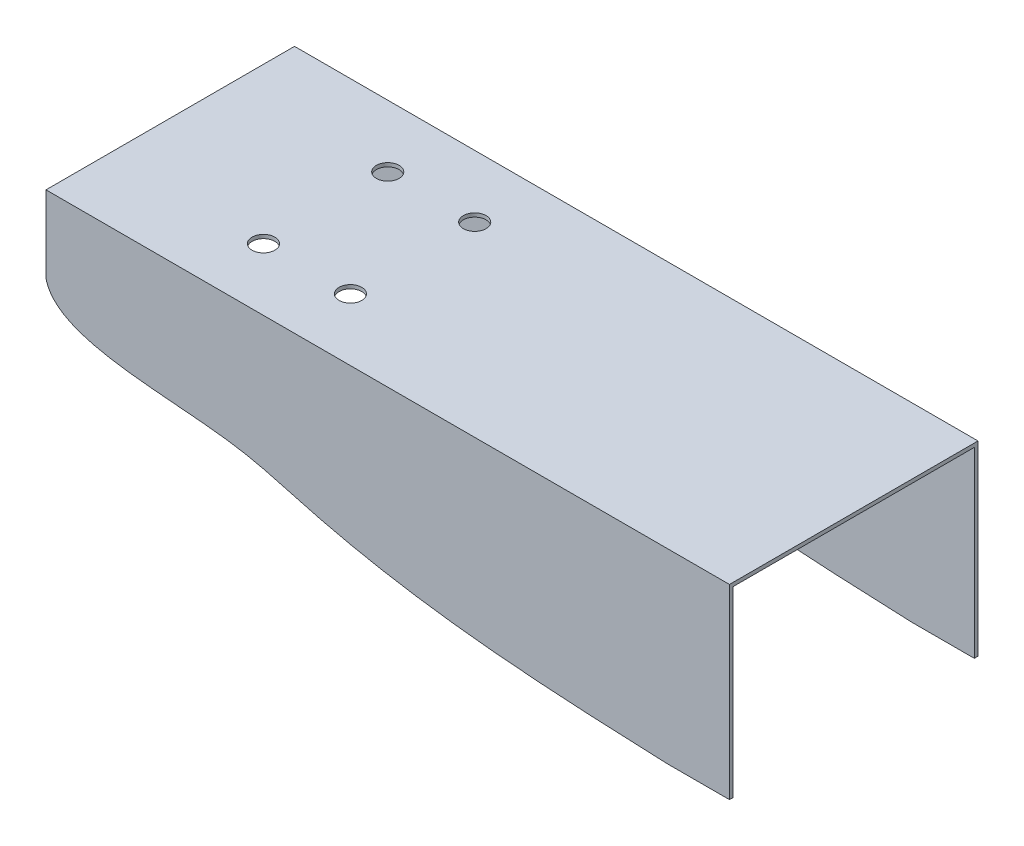
SolidWorks part; units mm, degrees
ref_plane "Спереди" through (0, 0, 0) normal (0, 0, 1) x (1, 0, 0)
ref_plane "Сверху" through (0, 0, 0) normal (0, 1, 0) x (1, 0, 0)
ref_plane "Справа" through (0, 0, 0) normal (1, 0, 0) x (0, 0, -1)
sketch "Эскиз1" plane through (0, 0, 0) normal (1, 0, 0) x (0, 0, -1)
  line L0 (0, 0) -> (0, 150)
  line L1 (0, 150) -> (200, 150)
  line L2 (200, 150) -> (200, 0)
extrude "Вытянуть-Тонкостенный1" add sketch "Эскиз1" along normal blind 550 thin thin type one direction wall 3
sketch "Эскиз2" plane through (0, 0, 0) normal (0, 0, 1) x (1, 0, 0)
  line L0 (0, 88.193) -> (0, 0)
  line L1 (0, 0) -> (0, 150) construction
  line L2 (0, 0) -> (500, 0)
  line L3 (550, 0) -> (0, 0) construction
  spline S0 degree 3 poles (500, 0) (390.3536, 4.2394) (282.8925, 10.5537) (127.1973, 58.204) (8.8444, 51.1437) (0, 88.193) knots 0 0 0 0 0.609013 0.709013 1 1 1 1
extrude "Вырез-Вытянуть1" cut sketch "Эскиз2" against normal through all
sketch "Эскиз3" plane through (0, 150, 0) normal (0, 1, 0) x (1, 0, 0)
  circle A0 centre (125, 150) radius 9.1442
  circle A1 centre (125, 50) radius 9.1442
  circle A2 centre (195, 50) radius 9.1442
  circle A3 centre (195, 150) radius 9.1442
  dimension "D1" = 2
  dimension "D2" = 2
extrude "Вырез-Вытянуть2" cut sketch "Эскиз3" against normal blind 10
